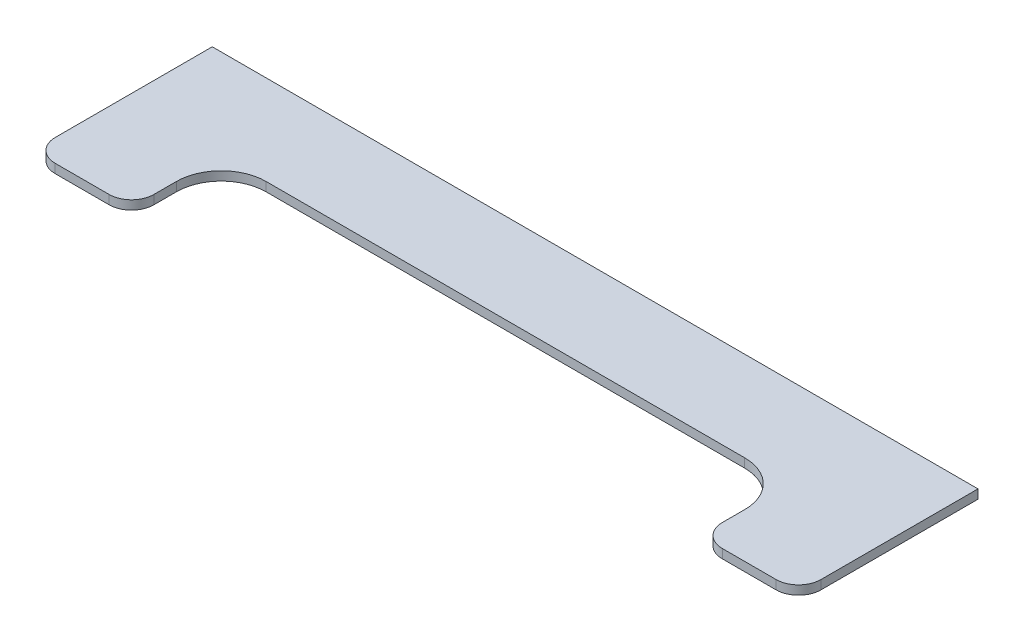
SolidWorks part; units mm, degrees
material "Клен"
ref_plane "Спереди" through (0, 0, 0) normal (0, 0, 1) x (1, 0, 0)
ref_plane "Сверху" through (0, 0, 0) normal (0, 1, 0) x (1, 0, 0)
ref_plane "Справа" through (0, 0, 0) normal (1, 0, 0) x (0, 0, -1)
sketch "Эскиз1" plane through (0, 0, 0) normal (0, 1, 0) x (1, 0, 0)
  line L0 (-330.2029, 15) -> (-330.2029, 120)
  line L5 (-330.2029, 120) -> (181.7971, 120)
  line L6 (181.7971, 120) -> (181.7971, 15)
  line L7 (166.7971, 0) -> (130.7971, 0)
  line L8 (115.7971, 15) -> (115.7971, 30)
  line L9 (85.7971, 60) -> (-234.2029, 60)
  line L10 (-264.2029, 30) -> (-264.2029, 15)
  line L11 (-279.2029, 0) -> (-315.2029, 0)
  arc A0 (-234.2029, 60) -> (-264.2029, 30) centre (-234.2029, 30) ccw
  arc A1 (115.7971, 30) -> (85.7971, 60) centre (85.7971, 30) ccw
  arc A2 (-264.2029, 15) -> (-279.2029, 0) centre (-279.2029, 15) cw
  arc A3 (130.7971, 0) -> (115.7971, 15) centre (130.7971, 15) cw
  arc A4 (-330.2029, 15) -> (-315.2029, 0) centre (-315.2029, 15) ccw
  arc A5 (181.7971, 15) -> (166.7971, 0) centre (166.7971, 15) cw
  point P10 (0, 0)
  point P13 (0, 0)
  point P14 (0, 0)
  point P17 (0, 0)
  point P22 (0, 0)
  dimension "D4" = 30
  dimension "D5" = 30
  dimension "D6" = 15
  dimension "D7" = 15
  dimension "D8" = 15
  dimension "D9" = 15
  dimension "D1" = 512
  dimension "D2" = 120
  dimension "D3" = 66
  dimension "D10" = 60
extrude "Бобышка-Вытянуть1" add sketch "Эскиз1" along normal blind 6
